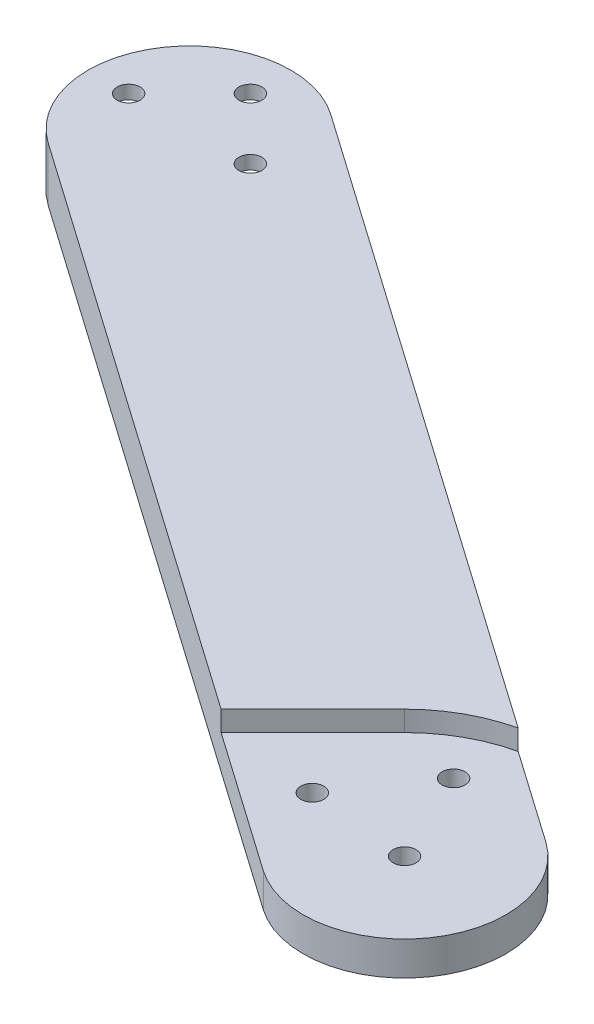
SolidWorks part; units mm, degrees
ref_plane "Front Plane" through (0, 0, 0) normal (0, 0, 1) x (1, 0, 0)
ref_plane "Top Plane" through (0, 0, 0) normal (0, 1, 0) x (1, 0, 0)
ref_plane "Right Plane" through (0, 0, 0) normal (1, 0, 0) x (0, 0, -1)
sketch "Sketch1" plane through (0, 0, 0) normal (0, 1, 0) x (1, 0, 0)
  line L0 (0, 0) -> (106.066, 106.066) construction
  line L1 (3.4641, 17.5) -> (1.7321, 20.5)
  line L2 (1.7321, 20.5) -> (-1.7321, 20.5)
  line L3 (-1.7321, 20.5) -> (-3.4641, 17.5)
  line L4 (-3.4641, 17.5) -> (-1.7321, 14.5)
  line L5 (-1.7321, 14.5) -> (1.7321, 14.5)
  line L6 (1.7321, 14.5) -> (3.4641, 17.5)
  line L7 (-17.5, -3.4641) -> (-14.5, -1.7321)
  line L8 (-14.5, -1.7321) -> (-14.5, 1.7321)
  line L9 (-14.5, 1.7321) -> (-17.5, 3.4641)
  line L10 (-17.5, 3.4641) -> (-20.5, 1.7321)
  line L11 (-20.5, 1.7321) -> (-20.5, -1.7321)
  line L12 (-20.5, -1.7321) -> (-17.5, -3.4641)
  line L13 (-3.4641, -17.5) -> (-1.7321, -20.5)
  line L14 (-1.7321, -20.5) -> (1.7321, -20.5)
  line L15 (1.7321, -20.5) -> (3.4641, -17.5)
  line L16 (3.4641, -17.5) -> (1.7321, -14.5)
  line L17 (1.7321, -14.5) -> (-1.7321, -14.5)
  line L18 (-1.7321, -14.5) -> (-3.4641, -17.5)
  line L19 (17.5, 3.4641) -> (14.5, 1.7321)
  line L20 (14.5, 1.7321) -> (14.5, -1.7321)
  line L21 (14.5, -1.7321) -> (17.5, -3.4641)
  line L22 (17.5, -3.4641) -> (20.5, -1.7321)
  line L23 (20.5, -1.7321) -> (20.5, 1.7321)
  line L24 (20.5, 1.7321) -> (17.5, 3.4641)
  line L25 (-15.5563, 15.5563) -> (90.5097, 121.6224)
  line L26 (15.5563, -15.5563) -> (121.6224, 90.5097)
  line L27 (106.066, 106.066) -> (0, 180.3342) construction
  line L28 (97.4624, 93.7787) -> (-8.6036, 168.047)
  line L29 (114.6697, 118.3533) -> (8.6036, 192.6215)
  line L30 (99.7189, 119.6662) -> (91.1152, 107.3789) construction
  line L31 (106.9626, 109.4121) -> (103.6165, 108.5155)
  line L32 (103.6165, 108.5155) -> (102.72, 105.1694)
  line L33 (102.72, 105.1694) -> (105.1694, 102.72)
  line L34 (105.1694, 102.72) -> (108.5155, 103.6165)
  line L35 (108.5155, 103.6165) -> (109.4121, 106.9626)
  line L36 (109.4121, 106.9626) -> (106.9626, 109.4121)
  line L37 (-9, 180.3342) -> (9, 180.3342) construction
  line L38 (90.2186, 104.0328) -> (93.5647, 104.9294)
  line L39 (93.5647, 104.9294) -> (94.4613, 108.2754)
  line L40 (94.4613, 108.2754) -> (92.0118, 110.7249)
  line L41 (92.0118, 110.7249) -> (88.6657, 109.8284)
  line L42 (88.6657, 109.8284) -> (87.7692, 106.4823)
  line L43 (87.7692, 106.4823) -> (90.2186, 104.0328)
  line L44 (100.6154, 123.0122) -> (97.2694, 122.1156)
  line L45 (97.2694, 122.1156) -> (96.3728, 118.7696)
  line L46 (96.3728, 118.7696) -> (98.8223, 116.3201)
  line L47 (98.8223, 116.3201) -> (102.1684, 117.2167)
  line L48 (102.1684, 117.2167) -> (103.0649, 120.5627)
  line L49 (103.0649, 120.5627) -> (100.6154, 123.0122)
  line L50 (-3.4641, 17.5) -> (3.4641, 17.5)
  line L51 (-3.4641, 17.5) -> (-3.4641, 23.8539)
  line L52 (-3.4641, 23.8539) -> (3.4641, 23.8539)
  line L53 (3.4641, 17.5) -> (3.4641, 23.8539)
  line L54 (-17.5, -3.4641) -> (-25.5814, -3.4641)
  line L55 (-17.5, -3.4641) -> (-17.5, 3.4641)
  line L56 (-17.5, 3.4641) -> (-25.5814, 3.4641)
  line L57 (-25.5814, -3.4641) -> (-25.5814, 3.4641)
  line L58 (-3.4641, -17.5) -> (3.4641, -17.5)
  line L59 (-3.4641, -17.5) -> (-3.4641, -25.8241)
  line L60 (-3.4641, -25.8241) -> (3.4641, -25.8241)
  line L61 (3.4641, -17.5) -> (3.4641, -25.8241)
  line L62 (17.5, 3.4641) -> (24.0978, 3.4641)
  line L63 (17.5, 3.4641) -> (17.5, -3.4641)
  line L64 (17.5, -3.4641) -> (24.0978, -3.4641)
  line L65 (24.0978, 3.4641) -> (24.0978, -3.4641)
  line L66 (-111.8183, 250.0982) -> (111.8183, 250.0982)
  line L67 (-111.8183, 250.0982) -> (-111.8183, 175.3342)
  line L68 (-111.8183, 175.3342) -> (111.8183, 175.3342)
  line L69 (111.8183, 250.0982) -> (111.8183, 175.3342)
  line L70 (-15.8392, 15.8392) -> (90.2268, 121.9052)
  line L71 (15.8392, -15.8392) -> (121.9052, 90.2268)
  circle A0 centre (0, 0) radius 14
  circle A1 centre (0, 0) radius 21
  circle A2 centre (0, 0) radius 17.5 construction
  circle A3 centre (0, 17.5) radius 1.7
  circle A4 centre (17.5, 0) radius 1.7
  circle A5 centre (0, -17.5) radius 1.7
  circle A6 centre (-17.5, 0) radius 1.7
  circle A7 centre (0, 17.5) radius 3 construction
  circle A8 centre (-17.5, 0) radius 3 construction
  circle A9 centre (0, -17.5) radius 3 construction
  circle A10 centre (17.5, 0) radius 3 construction
  arc A12 (-15.5563, 15.5563) -> (15.5563, -15.5563) centre (0, 0) ccw
  arc A13 (121.6224, 90.5097) -> (90.5097, 121.6224) centre (106.066, 106.066) ccw
  arc A14 (97.4624, 93.7787) -> (114.6697, 118.3533) centre (106.066, 106.066) ccw
  arc A15 (8.6036, 192.6215) -> (-8.6036, 168.047) centre (0, 180.3342) ccw
  circle A16 centre (106.066, 106.066) radius 1.7
  circle A17 centre (106.066, 106.066) radius 3 construction
  circle A18 centre (99.7189, 119.6662) radius 1.7
  circle A19 centre (91.1152, 107.3789) radius 1.7
  circle A20 centre (91.1152, 107.3789) radius 3 construction
  circle A21 centre (99.7189, 119.6662) radius 3 construction
  circle A22 centre (0, 189.3342) radius 1.7
  circle A23 centre (9, 180.3342) radius 1.7
  circle A24 centre (-9, 180.3342) radius 1.7
  arc A25 (121.9052, 90.2268) -> (90.2268, 121.9052) centre (106.066, 106.066) ccw
  arc A26 (-15.8392, 15.8392) -> (15.8392, -15.8392) centre (0, 0) ccw
  point P14 (53.033, 53.033)
  point P50 (53.033, 143.2001)
  point P66 (95.417, 113.5225)
  point P102 (0, 180.3342)
  point P103 (-9.4501, 180.3342)
  dimension "D1" = 28
  dimension "D2" = 42
  dimension "D4" = 3.4
  dimension "D5" = 3.4
  dimension "D6" = 3.4
  dimension "D7" = 3.4
  dimension "D8" = 6
  dimension "D3" = 3.5
  dimension "D9" = 3.5
  dimension "D10" = 6
  dimension "D11" = 6
  dimension "D12" = 6
  dimension "D13" = 22
  dimension "D17" = 15
  dimension "D18" = 3.4
  dimension "D19" = 6
  dimension "D20" = 3.4
  dimension "D22" = 3.4
  dimension "D23" = 6
  dimension "D24" = 6
  dimension "D29" = 3.4
  dimension "D30" = 3.4
  dimension "D31" = 3.4
  dimension "D14" = 45
  dimension "D15" = 150
  dimension "D16" = 80
  dimension "D21" = 15
  dimension "D25" = 13
  dimension "D26" = 5
  dimension "D27" = 9
  dimension "D28" = 9
  dimension "D32" = 0.4
extrude "Boss-Extrude1" add sketch "Sketch1" along normal blind 8 contours L28 A15 L29 A14
extrude "Cut-Extrude1" cut sketch "Sketch1<11>" against normal blind 3 from surface contours A25 L70 A26 L71 starting at face at (53.033, 8, -143.2001)
sketch "Sketch1<11>" plane through (0, 0, 0) normal (0, 1, 0) x (1, 0, 0) same geometry as "Sketch1"
extrude "Cut-Extrude2" cut sketch "Sketch1<12>" along normal blind 6 contours L29 A15 L68 A24 A23 A22 region at (4.3544, 0, -183.2924)
sketch "Sketch1<12>" plane through (0, 0, 0) normal (0, 1, 0) x (1, 0, 0) same geometry as "Sketch1"
extrude "Cut-Extrude3" cut sketch "Sketch1<13>" along normal through all both and the other way through all contours A22 | A24 | A23 | A18 | A19 | A16 region at (106.066, 0, -106.066) region at (99.7189, 0, -119.6662) region at (91.1152, 0, -107.3789) region at (0, 0, -189.3342) region at (9, 0, -180.3342) region at (-9, 0, -180.3342)
sketch "Sketch1<13>" plane through (0, 0, 0) normal (0, 1, 0) x (1, 0, 0) same geometry as "Sketch1"
